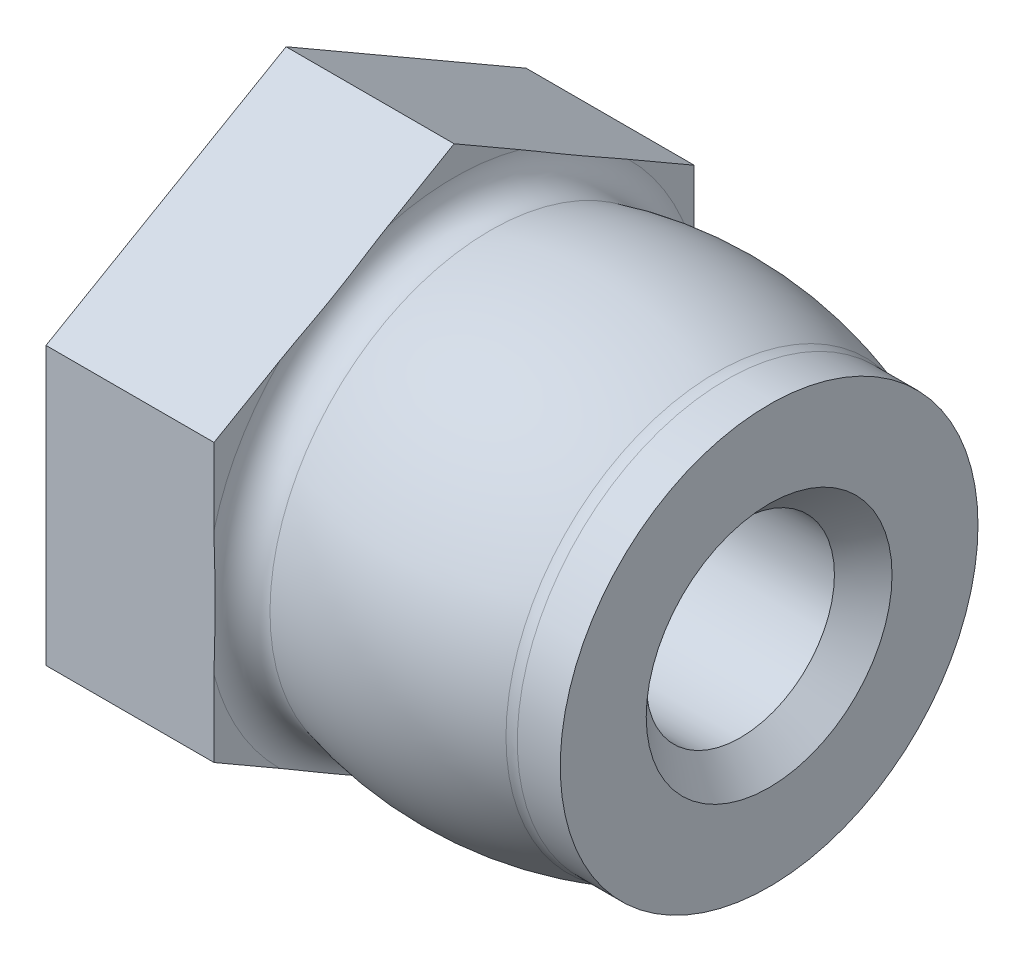
SolidWorks part; units mm, degrees
material "Rubber"
ref_plane "Front Plane" through (0, 0, 0) normal (0, 0, 1) x (1, 0, 0)
ref_plane "Top Plane" through (0, 0, 0) normal (0, 1, 0) x (1, 0, 0)
ref_plane "Right Plane" through (0, 0, 0) normal (1, 0, 0) x (0, 0, -1)
sketch "Sketch1" plane through (0, 0, 0) normal (0, 0, 1) x (1, 0, 0)
  line L0 (0, -60.3389) -> (0, 2956.6067) construction
  line L1 (-60.3389, 0) -> (2956.6067, 0) construction
  line L2 (0, 1.2446) -> (-5.7531, 1.2446)
  line L3 (-5.7531, 1.2446) -> (-5.7531, 3.175)
  line L4 (-5.7531, 3.175) -> (-3.5306, 3.175)
  line L5 (-3.5306, 3.175) -> (-3.5306, 2.7622)
  line L6 (0, 1.2446) -> (0, 2.7622)
  arc A0 (0, 2.7622) -> (-3.5306, 2.7622) centre (-1.7653, -2.0012) ccw
  dimension "D6" = 5.08
  dimension "D1" = 3.175
  dimension "D2" = 2.4892
  dimension "D3" = 2.2225
  dimension "D4" = 3.9878
  dimension "D5" = 5.5245
revolve "Revolve1" add sketch "Sketch1" angle 360 about L1
sketch "Sketch2" plane through (-5.7531, 0, 0) normal (-1, 0, 0) x (0, 0, 1)
  line L1 (3.175, -1.8331) -> (3.175, 1.8331)
  line L2 (3.175, 1.8331) -> (0, 3.6662)
  line L3 (0, 3.6662) -> (-3.175, 1.8331)
  line L4 (-3.175, 1.8331) -> (-3.175, -1.8331)
  line L5 (-3.175, -1.8331) -> (0, -3.6662)
  line L6 (0, -3.6662) -> (3.175, -1.8331)
  circle A0 centre (0, 0) radius 3.175 construction
  circle A1 centre (0, 0) radius 3.175 construction
  circle M7 centre (0, 0) radius 1.2446
  circle M8 centre (0, 0) radius 3.175
extrude "Boss-Extrude1" add sketch "Sketch2" against normal up to surface (2.2225 mm away) contours L2 L3 M8 | L1 L2 M8 | L6 L1 M8 | L5 L6 M8 | L4 L5 M8 | L3 L4 M8 | M8 M7 region at (-5.7531, -1.6408, 2.8419) region at (-5.7531, 1.6408, 2.8419) region at (-5.7531, -1.5426, 2.6719) region at (-5.7531, -3.2816, 0) region at (-5.7531, 3.2816, 0) region at (-5.7531, -1.6408, -2.8419) region at (-5.7531, 1.6408, -2.8419) up to face at (-3.5306, 0, 3.175)
sketch "Sketch3" plane through (0, 0, 0) normal (1, 0, 0) x (0, 0, -1)
  circle A0 centre (0, 0) radius 1.2446
  circle A1 centre (0, 0) radius 2.7623
  circle A2 centre (0, 0) radius 2.7623
  circle A3 centre (0, 0) radius 1.2446
extrude "Boss-Extrude2" add sketch "Sketch3" along normal blind 0.635
fillet "Fillet1" radius 0.381 1 edges at (-3.5306, 0, 2.7622) type face fillet first side face at (-3.5306, 0, 0) second side face at (-3.5306, 0, 2.7622)
fillet "Fillet2" radius 0.381 1 edges at (0, 0, -2.7623)
chamfer "Chamfer1" distance 0.381 angle 45 1 edges at (0.635, 0, -1.2446)
